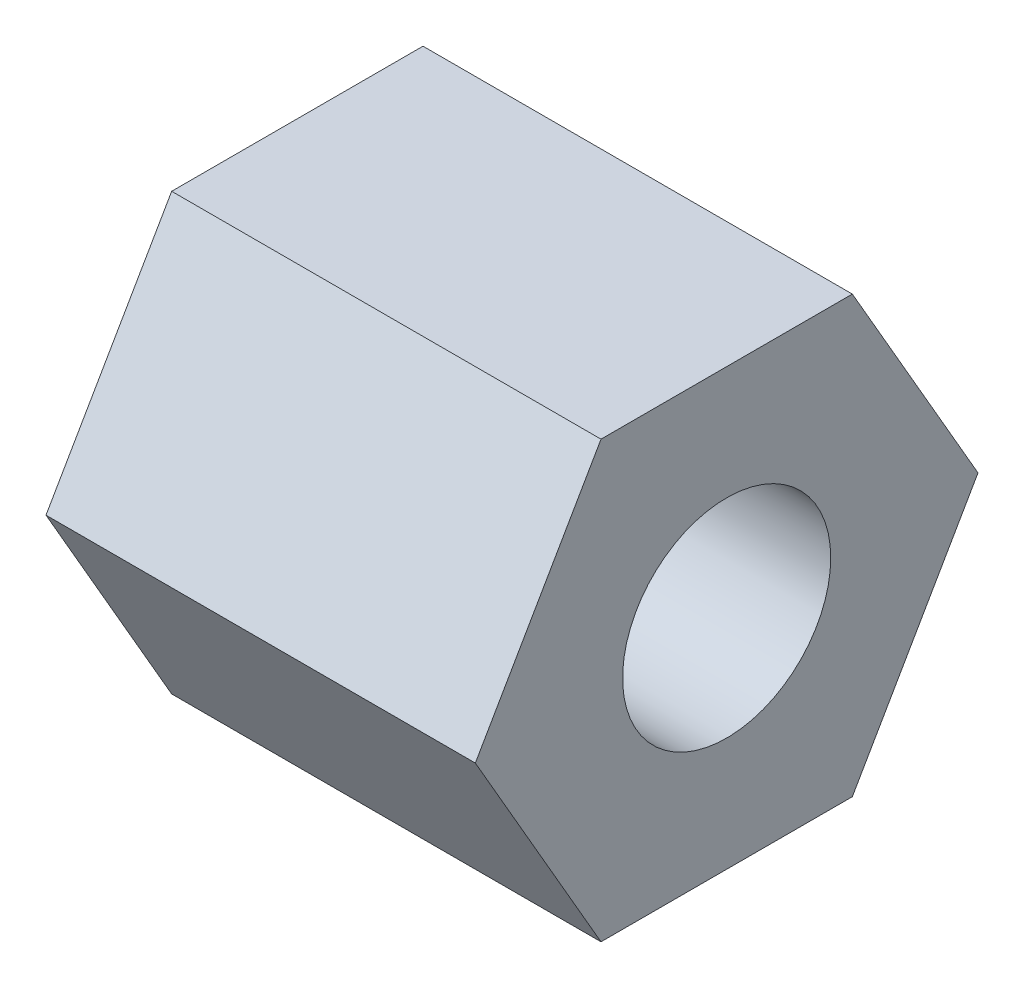
SolidWorks part; units mm, degrees
material "6061-T4 (SS)"
ref_plane "Front Plane" through (0, 0, 0) normal (0, 0, 1) x (1, 0, 0)
ref_plane "Top Plane" through (0, 0, 0) normal (0, 1, 0) x (1, 0, 0)
ref_plane "Right Plane" through (0, 0, 0) normal (1, 0, 0) x (0, 0, -1)
sketch "Sketch1" plane through (0, 0, 0) normal (1, 0, 0) x (0, 0, -1)
  line L0 (0, 0) -> (2.9445, 0) construction
  line L1 (2.9445, 0) -> (1.4722, 2.55)
  line L2 (1.4722, 2.55) -> (-1.4722, 2.55)
  line L3 (-1.4722, 2.55) -> (-2.9445, 0)
  line L4 (-2.9445, 0) -> (-1.4722, -2.55)
  line L5 (-1.4722, -2.55) -> (1.4722, -2.55)
  line L6 (1.4722, -2.55) -> (2.9445, 0)
  circle A0 centre (0, 0) radius 2.55 construction
  point P1 (-2.2084, 1.275)
  dimension "D1" = 5.1
extrude "Boss-Extrude1" add sketch "Sketch1" along normal blind 5.03
sketch "Sketch2" plane through (5.03, 0, 0) normal (1, 0, 0) x (0, 0, -1)
  circle A0 centre (0, 0) radius 1.0922
  dimension "D1" = 2.1844
hole_wizard "#2 Clearance Hole1" positions "Sketch3" profile "Sketch4" hole size "#2" standard "ANSI Inch" end condition through all
sketch "Sketch3" plane through (5.03, 0, 0) normal (1, 0, 0) x (0, 0, -1)
  point P0 (0, 0)
sketch "Sketch4" plane through (5.03, 0, 0) normal (0, 1, 0) x (0, 0, -1)
  line L0 (0, 0) -> (0, 5.03)
  line L1 (0, 5.03) -> (1.2192, 5.03)
  line L2 (1.2192, 5.03) -> (1.2192, 0)
  line L5 (1.2192, 0) -> (0, 0)
  line L11 (0, -6.35) -> (0, 107.95) construction
  dimension "Thru Hole Dia." = 2.4384
  dimension "Thru Hole Depth" = 5.03
